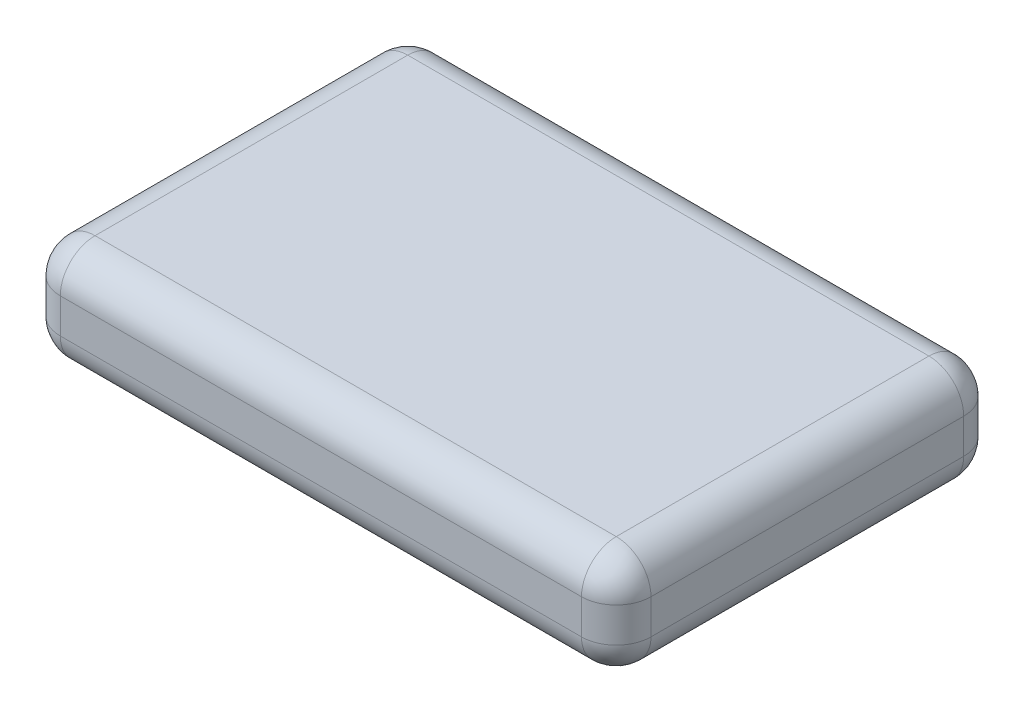
SolidWorks part; units mm, degrees
ref_plane "Front Plane" through (0, 0, 0) normal (0, 0, 1) x (1, 0, 0)
ref_plane "Top Plane" through (0, 0, 0) normal (0, 1, 0) x (1, 0, 0)
ref_plane "Right Plane" through (0, 0, 0) normal (1, 0, 0) x (0, 0, -1)
sketch "Sketch1" plane through (0, 0, 0) normal (0, 1, 0) x (1, 0, 0)
  line L1 (-85, 55) -> (85, 55)
  line L2 (-85, 55) -> (-85, -55)
  line L3 (-85, -55) -> (85, -55)
  line L4 (85, 55) -> (85, -55)
  line L5 (-85, 55) -> (85, -55) construction
  line L6 (-85, -55) -> (85, 55) construction
  point P0 (0, 0)
  dimension "D1" = 170
  dimension "D2" = 110
extrude "Boss-Extrude1" add sketch "Sketch1" along normal blind 30
fillet "Fillet2" radius 10 5 edges at (-85, 15, 55) (0, 30, 55) (85, 15, 55) (0, 0, 55) (-85, 30, 0)
fillet "Fillet3" radius 10 6 edges at (82.0711, 27.0711, 52.0711) (-85, 10, -55) (-82.0711, 27.0711, -55) (85, 30, -5) (85, 15, -55) (5, 30, -55)
fillet "Fillet4" radius 10 7 edges at (82.0711, 2.9289, 52.0711) (-82.0711, 2.9289, 52.0711) (-85, 0, 0) (-82.0711, 0, -52.0711) (82.0711, 0, -52.0711) (0, 0, -55) (85, 0, 0)
